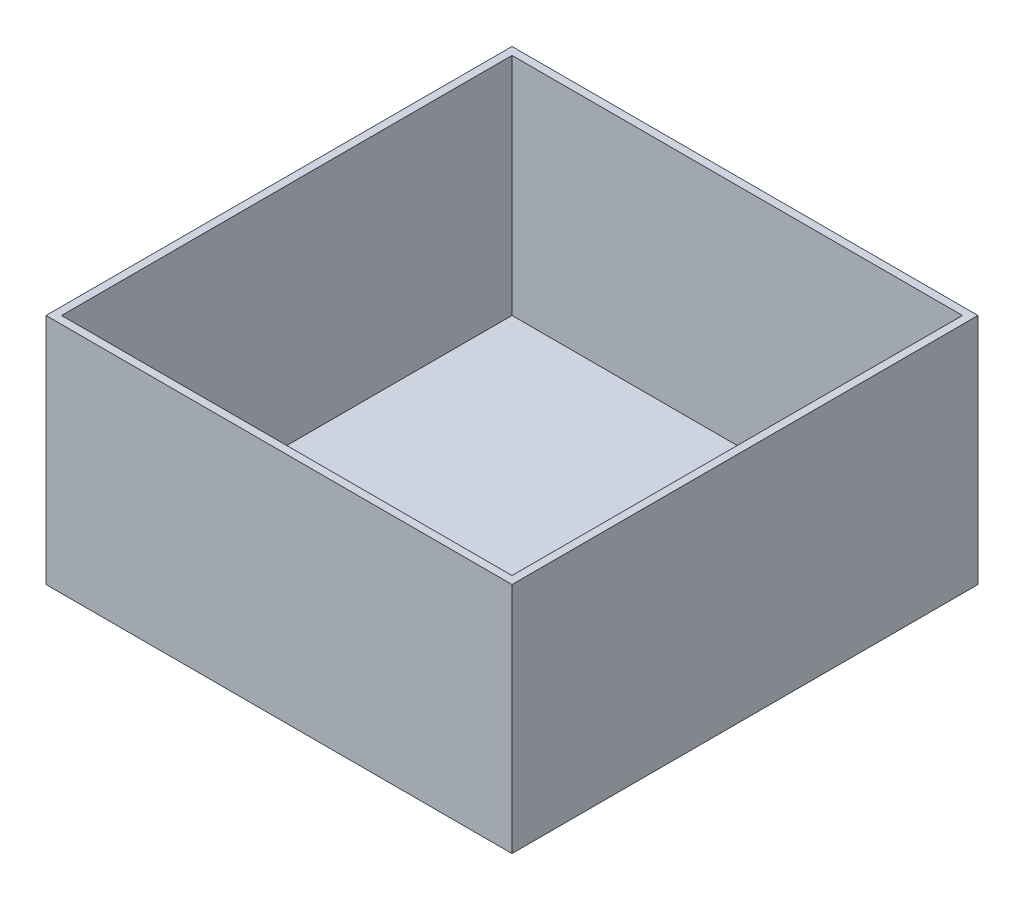
SolidWorks part; units mm, degrees
ref_plane "Front Plane" through (0, 0, 0) normal (0, 0, 1) x (1, 0, 0)
ref_plane "Top Plane" through (0, 0, 0) normal (0, 1, 0) x (1, 0, 0)
ref_plane "Right Plane" through (0, 0, 0) normal (1, 0, 0) x (0, 0, -1)
sketch "Sketch1" plane through (0, 0, 0) normal (0, 1, 0) x (1, 0, 0)
  line L1 (-60, -60) -> (60, -60)
  line L2 (-60, -60) -> (-60, 60)
  line L3 (-60, 60) -> (60, 60)
  line L4 (60, -60) -> (60, 60)
  line L5 (-60, -60) -> (60, 60) construction
  line L6 (-60, 60) -> (60, -60) construction
  point P0 (0, 0)
  dimension "D1" = 120
  dimension "D2" = 120
extrude "Boss-Extrude1" add sketch "Sketch1" along normal blind 60
shell "Shell1" thickness 2 removed face at (0, 60, 0)
